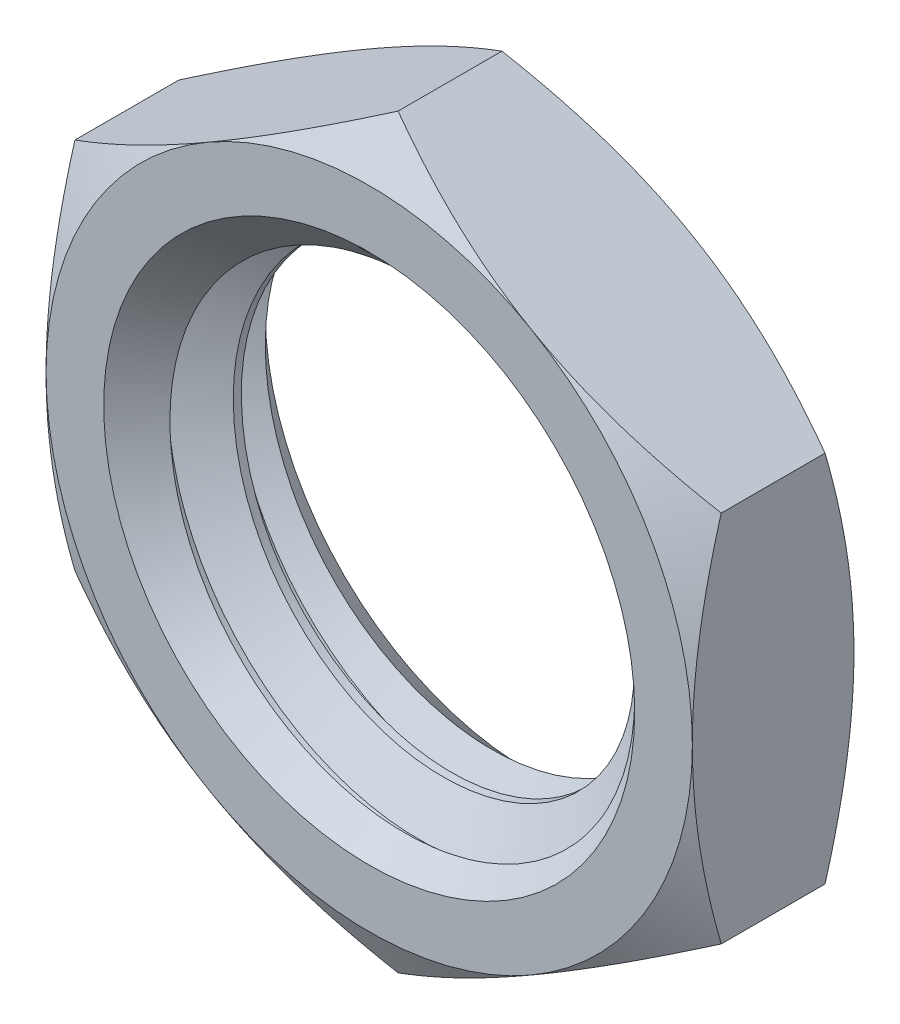
SolidWorks part; units mm, degrees
ref_plane "Front Plane" through (0, 0, 0) normal (0, 0, 1) x (1, 0, 0)
ref_plane "Top Plane" through (0, 0, 0) normal (0, 1, 0) x (1, 0, 0)
ref_plane "Right Plane" through (0, 0, 0) normal (1, 0, 0) x (0, 0, -1)
sketch "Sketch1" plane through (0, 0, 0) normal (0, 0, 1) x (1, 0, 0)
  line L1 (0, 4.5827) -> (-3.9688, 2.2914)
  line L2 (-3.9688, 2.2914) -> (-3.9688, -2.2914)
  line L3 (-3.9688, -2.2914) -> (0, -4.5827)
  line L4 (0, -4.5827) -> (3.9687, -2.2914)
  line L5 (3.9687, -2.2914) -> (3.9687, 2.2914)
  line L6 (3.9687, 2.2914) -> (0, 4.5827)
  circle A0 centre (0, 0) radius 3.9688 construction
  circle A1 centre (0, 0) radius 3.175
  dimension "Screw Size" = 6.35
  dimension "Hex Size" = 7.9375
extrude "Boss-Extrude1" add sketch "Sketch1" along normal mid plane 1.9844
sketch "Sketch2" plane through (0, 0, 0.9922) normal (0, 0, 1) x (1, 0, 0)
  circle A2 centre (0, 0) radius 3.9688 construction
  circle A3 centre (0, 0) radius 3.9688
extrude "Cut-Extrude1" cut sketch "Sketch2" against normal through all draft 60 flip side to cut
sketch "Sketch3" plane through (0, 0, -0.9922) normal (0, 0, -1) x (-1, 0, 0)
  circle A0 centre (0, 0) radius 3.9688 construction
  circle A1 centre (0, 0) radius 3.9688
extrude "Cut-Extrude2" cut sketch "Sketch3" against normal through all draft 60 flip side to cut
sketch "Sketch4" plane through (0, 0, 0.9922) normal (0, 0, 1) x (1, 0, 0)
  circle A0 centre (0, 0) radius 3.175 construction
  circle A1 centre (0, 0) radius 3.175
curve "Helix/Spiral2" pitch 0.7937 height 2.7781 radius 3.175 centre (0, 0, 0.9922) axis (0, 0, -1) start towards (0, 1, 0) parameters "Pitch"=0.7937
sketch "Sketch5" plane through (0, 0, 0) normal (1, 0, 0) x (0, 0, -1)
  line L0 (-1.7363, 3.2609) -> (-0.9426, 3.2609) construction
  line L1 (-0.9426, 3.2609) -> (-1.3395, 2.5735) construction
  line L2 (-1.3395, 2.5735) -> (-1.7363, 3.2609) construction
  line L3 (-1.3395, 2.5735) -> (-1.3395, 2.6594) construction
  line L4 (-1.3395, 3.2609) -> (-1.3395, 3.175) construction
  line L5 (-1.3891, 2.6594) -> (-1.2898, 2.6594) construction
  line L6 (-1.6867, 3.175) -> (-0.9922, 3.175) construction
  line L7 (-1.7115, 3.218) -> (-0.9674, 3.218) construction
  line L8 (-1.7115, 3.218) -> (-0.9674, 3.218)
  line L9 (-0.9674, 3.218) -> (-1.2898, 2.6594)
  line L10 (-1.2898, 2.6594) -> (-1.3891, 2.6594)
  line L11 (-1.3891, 2.6594) -> (-1.7115, 3.218)
  point P9 (-1.3395, 2.6594)
  point P14 (-1.3395, 3.175)
  point P15 (-1.3395, 3.218)
  dimension "D1" = 0.7937
  dimension "D2" = 0.0992
sweep "Sweep3" add profiles "Sketch5" path "Helix/Spiral2"
sketch "Sketch6" plane through (0, 0, 0.9922) normal (0, 0, 1) x (1, 0, 0)
  circle A0 centre (0, 0) radius 3.2609
extrude "Cut-Extrude3" cut sketch "Sketch6" against normal through all draft 45 and the other way through all
sketch "Sketch7" plane through (0, 0, -0.9922) normal (0, 0, -1) x (-1, 0, 0)
  circle A1 centre (0, 0) radius 3.2609
  circle A2 centre (0, 0) radius 3.2609
  dimension "D1" = 0
extrude "Cut-Extrude4" cut sketch "Sketch7" against normal through all draft 45 and the other way through all
ref_axis "Center Axis 1" through (0, 0, -1.5571) along (0, 0, 1)
ref_plane "Contact Plane 1" through (0, 0, 0.9922) normal (0, 0, 1) x (1, 0, 0)
ref_plane "Contact Plane 2" through (0, 0, -0.9922) normal (0, 0, -1) x (-1, 0, 0)
ref_axis "Axis1" through (0, 0, 1.0896) along (0, 0, -1)
equation "\"D3@Helix/Spiral2\" = \"Pitch@Helix/Spiral2\" + \"Width@Boss-Extrude1\""
equation "\"D1@Sketch5\" = \"Pitch@Helix/Spiral2\""
equation "\"D2@Sketch5\"= \"D1@Sketch5\"/8"
